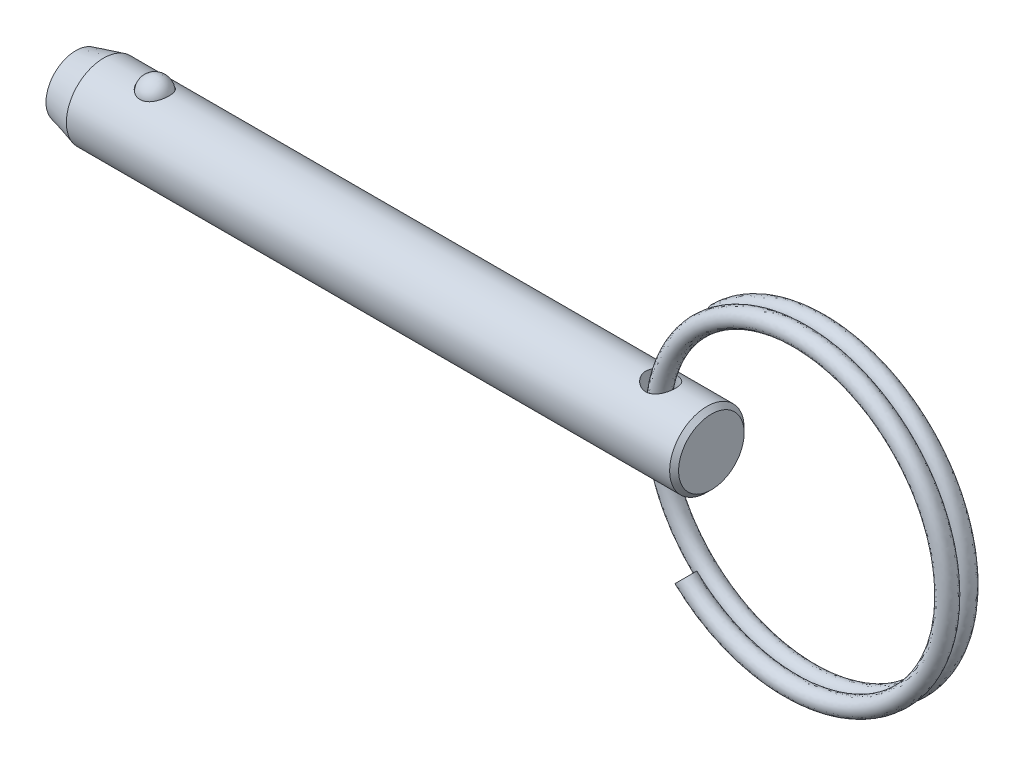
SolidWorks part; units mm, degrees
ref_plane "Front" through (0, 0, 0) normal (0, 0, 1) x (1, 0, 0)
ref_plane "Top" through (0, 0, 0) normal (0, 1, 0) x (1, 0, 0)
ref_plane "Right" through (0, 0, 0) normal (1, 0, 0) x (0, 0, -1)
sketch "Sketch1" plane through (0, 0, 0) normal (0, 0, 1) x (1, 0, 0)
  line L0 (27.0764, 2.794) -> (26.6954, 3.175)
  line L1 (26.6954, 3.175) -> (27.0764, 3.175) construction
  line L4 (27.0764, 2.794) -> (27.0764, 0)
  line L5 (27.0764, 3.175) -> (27.0764, 2.794) construction
  line L16 (26.6954, 3.175) -> (-24.7065, 3.175)
  line L17 (-27.0764, 3.175) -> (-27.0764, 2.54) construction
  line L19 (-24.7065, 3.175) -> (-27.0764, 3.175) construction
  line L22 (-27.0764, -3.175) -> (-24.7065, -3.175) construction
  line L23 (-20.3419, 2.8575) -> (-20.3419, -2.8575) construction
  line L24 (-27.0764, 0) -> (27.0764, 0)
  line L27 (27.0764, 0) -> (29.8704, 0) construction
  line L29 (-27.0764, 0) -> (-27.0764, -2.54) construction
  line L36 (21.4884, 0) -> (21.4884, 3.175) construction
  line L37 (-27.0764, 2.54) -> (-27.0764, 0)
  line L38 (-24.7065, -3.175) -> (27.0764, -3.175) construction
  line L39 (-27.0764, -2.54) -> (-27.0764, -3.175) construction
  line L40 (-24.7065, 3.175) -> (-27.0764, 2.54)
  line L42 (-24.7065, -3.175) -> (-27.0764, -2.54) construction
  line L43 (-24.7065, 3.175) -> (-24.7065, -3.175) construction
  circle A2 centre (-20.3419, 2.8575) radius 1.2319 construction
  point P35 (-19.1516, 3.175)
  dimension "A1" = 15
revolve "Revolve1" add sketch "Sketch1" angle 360 about L27
sketch "Sketch2" plane through (0, 0, 0) normal (0, 0, 1) x (1, 0, 0)
  line L0 (-19.0846, 2.8575) -> (-21.5992, 2.8575)
  line L1 (-20.3419, 4.0894) -> (-20.3419, 4.1148) construction
  line L2 (-19.0846, 2.8575) -> (-16.57, 2.8575) construction
  circle A0 centre (-20.3419, 2.8575) radius 1.2319 construction
  circle A1 centre (-20.3419, 2.8575) radius 1.2319 construction
  arc A2 (-21.5992, 2.8575) -> (-19.0846, 2.8575) centre (-20.3419, 2.8575) cw
  dimension "D1" = 0.0254
revolve "Cut-Revolve1" cut sketch "Sketch2" angle 360 about L2
sketch "Sketch3" plane through (0, 0, 0) normal (0, 0, 1) x (1, 0, 0)
  line L0 (-19.11, 2.8575) -> (-21.5738, 2.8575)
  line L1 (-19.11, 2.8575) -> (-16.6462, 2.8575) construction
  circle A0 centre (-20.3419, 2.8575) radius 1.2319 construction
  arc A1 (-19.11, 2.8575) -> (-21.5738, 2.8575) centre (-20.3419, 2.8575) ccw
revolve "Revolve2" add sketch "Sketch3" angle 360 about L1
sketch "Sketch4" plane through (0, 0, 0) normal (0, 0, 1) x (1, 0, 0)
  line L1 (22.7584, -3.175) -> (24.0284, -3.175)
  line L2 (22.7584, -3.175) -> (22.7584, 3.175)
  line L3 (22.7584, 3.175) -> (24.0284, 3.175)
  line L4 (24.0284, -3.175) -> (24.0284, 3.175)
  line L5 (22.7584, -3.175) -> (22.7584, -4.445) construction
  line L6 (24.0284, 3.175) -> (27.0764, 3.175) construction
  line L8 (21.4884, -3.175) -> (21.4884, 3.175) construction
  line L9 (21.4884, 0) -> (22.7584, 0) construction
  line L11 (22.7584, 0) -> (24.0284, 0) construction
  line L12 (26.6954, 3.175) -> (-24.7065, 3.175) construction
  line L14 (-24.7065, -3.175) -> (27.0764, -3.175) construction
  dimension "D1" = 2.54
revolve "Cut-Revolve2" cut sketch "Sketch4" angle 360 about L2
sketch "Sketch5" plane through (0, 0, 0) normal (0, 0, 1) x (1, 0, 0)
  line L0 (0, 0) -> (21.7814, 0) construction
  line L1 (21.7814, 0) -> (21.7814, 3.175) construction
  line L2 (26.6954, 3.175) -> (-24.7065, 3.175) construction
  line L3 (35.2434, 0) -> (48.7054, 0) construction
  line L4 (24.0284, 3.175) -> (23.7354, 3.175) construction
  line L5 (22.7584, 3.175) -> (24.0284, 3.175) construction
  line L6 (22.1612, 3.175) -> (22.1612, -3.175) construction
  line L7 (21.7814, 3.175) -> (21.4884, 3.175) construction
  line L8 (22.7584, -3.175) -> (24.0284, -3.175) construction
  line L9 (22.1612, -3.175) -> (24.0284, -3.175) construction
  line L10 (21.7814, 0) -> (35.2434, 0) construction
  line L12 (23.7354, 3.175) -> (22.1612, 3.175) construction
  line L13 (35.2434, 11.938) -> (35.2434, 13.462) construction
  circle A0 centre (35.2434, 0) radius 13.462
  circle A1 centre (35.2434, 0) radius 11.938 construction
  circle A2 centre (35.2434, 0) radius 12.7 construction
  point P26 (35.2434, 12.7)
curve "Helix/Spiral1" pitch 1.5494 height 1.3557 radius 13.462 left hand yes centre (35.2434, 0, 0) axis (0, 0, -1) start towards (1, 0, 0)
sketch "Sketch6" plane through (114.0038, 0, 0) normal (0, 1, 0) x (0, 0, -1)
  line L0 (0, 90.6984) -> (0, 91.4604) construction
  line L1 (0, 91.4604) -> (0, 92.2224) construction
  circle A0 centre (0, 91.4604) radius 0.762
  dimension "D1" = 1.524
sketch "Sketch7" plane through (0, 0, 0) normal (0, 0, 1) x (1, 0, 0)
  circle A0 centre (35.2434, 0) radius 13.462 construction
  circle A1 centre (35.2434, 0) radius 13.462
curve "Helix/Spiral2" pitch 1.5494 height 1.3557 radius 13.462 left hand yes centre (35.2434, 0, 0) axis (0, 0, 1) start towards (1, 0, 0)
sweep "Sweep1" add profiles "Sketch6" path "Helix/Spiral1"
sweep "Sweep2" add profiles "Sketch6<2>" path "Helix/Spiral2"
sketch "Sketch6<2>" plane through (114.0038, 0, 0) normal (0, 1, 0) x (0, 0, -1) same geometry as "Sketch6"
equation "\"D12@Sketch1\"=\"A@Sketch1\" * 0.80"
equation "\"D2@Sketch1\"=\"A@Sketch1\" * 0.9"
equation "\"D1@Sketch4\" = \"A@Sketch1\" / 2.5"
equation "\"Ring OD@Sketch5\" = \"R Ring Dia@Sketch5\" * 0.06"
equation "\"D4@Helix/Spiral1\"=\"Ring OD@Sketch5\" + 0.001"
equation "\"D1@Sketch6\"=\"Ring OD@Sketch5\""
equation "\"D4@Helix/Spiral2\" = \"D4@Helix/Spiral1\""
equation "\"D5@Helix/Spiral2\" = \"D5@Helix/Spiral1\""
